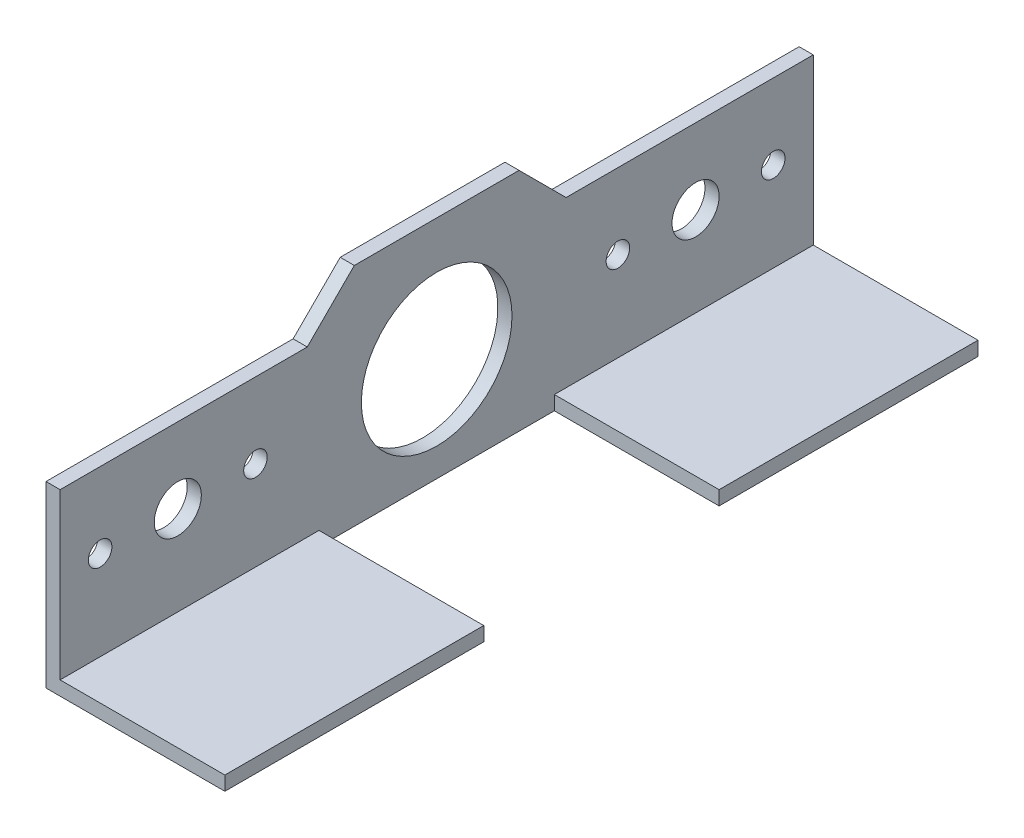
SolidWorks part; units mm, degrees
ref_plane "Alzado" through (0, 0, 0) normal (0, 0, 1) x (1, 0, 0)
ref_plane "Planta" through (0, 0, 0) normal (0, 1, 0) x (1, 0, 0)
ref_plane "Vista lateral" through (0, 0, 0) normal (1, 0, 0) x (0, 0, -1)
sketch "Croquis1" plane through (0, 0, 0) normal (0, 0, 1) x (1, 0, 0)
  line L0 (0, 0) -> (0, 38)
  line L1 (0, 0) -> (38, 0)
  line L2 (3, 3) -> (38, 3)
  line L3 (3, 3) -> (3, 38)
  line L4 (0, 38) -> (3, 38)
  line L5 (38, 3) -> (38, 0)
  dimension "D1" = 38
  dimension "D2" = 3
extrude "Saliente-Extruir1" add sketch "Croquis1" along normal blind 80 and the other way blind 80
sketch "Croquis2" plane through (0, 3, 0) normal (0, 1, 0) x (1, 0, 0)
  line L0 (3, 0) -> (38, 0) construction
  line L1 (3, 80) -> (3, -80) construction
  line L2 (38, 80) -> (38, -80) construction
  line L3 (3, 25) -> (3, -25)
  line L4 (3, -25) -> (38, -25)
  line L5 (38, -25) -> (38, 25)
  line L6 (3, 25) -> (38, 25)
  dimension "D1" = 25
extrude "Cortar-Extruir1" cut sketch "Croquis2" against normal up to surface (3 mm away) up to face at (19, 0, 0)
sketch "Croquis3" plane through (0, 0, 0) normal (-1, 0, 0) x (0, 0, 1)
  circle A0 centre (71.5, 22) radius 2.5 construction
  circle A1 centre (55, 22) radius 5 construction
  circle A2 centre (38.5, 22) radius 2.5 construction
  circle A3 centre (-38.5, 22) radius 2.5 construction
  circle A4 centre (-55, 22) radius 5 construction
  circle A5 centre (-71.5, 22) radius 2.5 construction
  circle A6 centre (71.5, 22) radius 2.5
  circle A7 centre (55, 22) radius 5
  circle A8 centre (38.5, 22) radius 2.5
  circle A9 centre (-38.5, 22) radius 2.5
  circle A10 centre (-55, 22) radius 5
  circle A11 centre (-71.5, 22) radius 2.5
  circle A12 centre (0, 22) radius 11 construction
  circle A13 centre (0, 22) radius 11 construction
extrude "Cortar-Extruir2" cut sketch "Croquis3" against normal up to surface (3 mm away) up to face at (3, 11, 0)
sketch "Croquis4" plane through (0, 0, 0) normal (-1, 0, 0) x (0, 0, 1)
  line L0 (27.5, 38) -> (17.5, 48) construction
  line L1 (-17.5, 48) -> (17.5, 48) construction
  line L2 (-17.5, 48) -> (-27.5, 38) construction
  line L3 (27.5, 38) -> (17.5, 48)
  line L4 (-17.5, 48) -> (17.5, 48)
  line L5 (-17.5, 48) -> (-27.5, 38)
  line L6 (-27.5, 38) -> (27.5, 38)
extrude "Saliente-Extruir2" add sketch "Croquis4" against normal up to surface (3 mm away) up to face at (3, 22, 69)
sketch "Croquis5" plane through (0, 0, 0) normal (-1, 0, 0) x (0, 0, 1)
  circle A0 centre (0, 22) radius 16
  dimension "D1" = 32
extrude "Cortar-Extruir3" cut sketch "Croquis5" against normal up to surface (3 mm away) up to face at (3, 22, 69)
